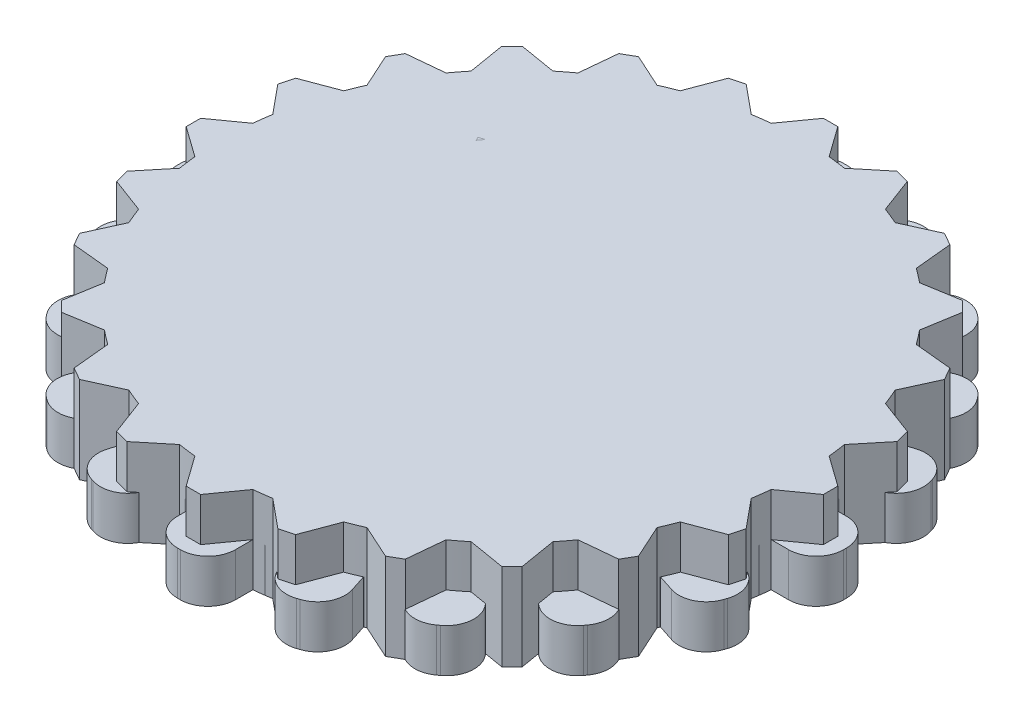
SolidWorks part; units mm, degrees
ref_plane "Front Plane" through (0, 0, 0) normal (0, 0, 1) x (1, 0, 0)
ref_plane "Top Plane" through (0, 0, 0) normal (0, 1, 0) x (1, 0, 0)
ref_plane "Right Plane" through (0, 0, 0) normal (1, 0, 0) x (0, 0, -1)
sketch "Sketch1" plane through (0, 0, 0) normal (0, 1, 0) x (1, 0, 0)
  line L86 (-3.1424, 4.8669) -> (1.8576, 4.8669)
  line L87 (-3.1424, 4.8669) -> (-3.1424, 1.8669)
  line L111 (-1.1424, 15.3669) -> (-0.1424, 15.3669)
  line L112 (-0.1424, 15.3669) -> (1.3576, 13.1649)
  line L113 (-1.1424, 15.3669) -> (-2.6424, 13.1649)
  line L114 (5.7906, 13.5092) -> (5.9886, 10.8522)
  line L115 (4.9246, 14.0092) -> (5.7906, 13.5092)
  line L116 (4.9246, 14.0092) -> (2.5245, 12.8522)
  line L117 (9.9999, 8.9339) -> (8.8429, 6.5338)
  line L118 (9.4999, 9.7999) -> (9.9999, 8.9339)
  line L119 (9.4999, 9.7999) -> (6.8429, 9.9979)
  line L120 (11.3576, 2.8669) -> (9.1556, 1.3669)
  line L121 (11.3576, 3.8669) -> (11.3576, 2.8669)
  line L122 (11.3576, 3.8669) -> (9.1556, 5.3669)
  line L123 (9.4999, -3.0661) -> (6.8429, -3.2641)
  line L124 (9.9999, -2.2001) -> (9.4999, -3.0661)
  line L125 (9.9999, -2.2001) -> (8.8429, 0.2)
  line L126 (4.9246, -7.2754) -> (2.5245, -6.1184)
  line L127 (5.7906, -6.7754) -> (4.9246, -7.2754)
  line L128 (5.7906, -6.7754) -> (5.9886, -4.1184)
  line L129 (-1.1424, -8.6331) -> (-2.6424, -6.4311)
  line L130 (-0.1424, -8.6331) -> (-1.1424, -8.6331)
  line L131 (-0.1424, -8.6331) -> (1.3576, -6.4311)
  line L132 (-7.0754, -6.7754) -> (-7.2734, -4.1184)
  line L133 (-6.2094, -7.2754) -> (-7.0754, -6.7754)
  line L134 (-6.2094, -7.2754) -> (-3.8093, -6.1184)
  line L135 (-11.2847, -2.2001) -> (-10.1277, 0.2)
  line L136 (-10.7847, -3.0661) -> (-11.2847, -2.2001)
  line L137 (-10.7847, -3.0661) -> (-8.1277, -3.2641)
  line L138 (-12.6424, 3.8669) -> (-10.4404, 5.3669)
  line L139 (-12.6424, 2.8669) -> (-12.6424, 3.8669)
  line L140 (-12.6424, 2.8669) -> (-10.4404, 1.3669)
  line L141 (-10.7847, 9.7999) -> (-8.1277, 9.9979)
  line L142 (-11.2847, 8.9339) -> (-10.7847, 9.7999)
  line L143 (-11.2847, 8.9339) -> (-10.1277, 6.5338)
  line L144 (-6.2094, 14.0092) -> (-3.8093, 12.8522)
  line L145 (-7.0754, 13.5092) -> (-6.2094, 14.0092)
  line L146 (-7.0754, 13.5092) -> (-7.2734, 10.8522)
  line L147 (-3.1424, 1.8669) -> (1.8576, 1.8669)
  line L148 (1.8576, 4.8669) -> (1.8576, 1.8669)
  line L149 (-3.1424, 4.8669) -> (1.8576, 1.8669) construction
  line L150 (-3.1424, 1.8669) -> (1.8576, 4.8669) construction
  arc A43 (-2.6424, 13.1649) -> (-3.8093, 12.8522) centre (-0.6424, 3.3669) ccw
  arc A44 (-7.2734, 10.8522) -> (-8.1277, 9.9979) centre (-0.6424, 3.3669) ccw
  arc A45 (-10.1277, 6.5338) -> (-10.4404, 5.3669) centre (-0.6424, 3.3669) ccw
  arc A46 (-10.4404, 1.3669) -> (-10.1277, 0.2) centre (-0.6424, 3.3669) ccw
  arc A47 (-8.1277, -3.2641) -> (-7.2734, -4.1184) centre (-0.6424, 3.3669) ccw
  arc A48 (-3.8093, -6.1184) -> (-2.6424, -6.4311) centre (-0.6424, 3.3669) ccw
  arc A49 (1.3576, -6.4311) -> (2.5245, -6.1184) centre (-0.6424, 3.3669) ccw
  arc A50 (5.9886, -4.1184) -> (6.8429, -3.2641) centre (-0.6424, 3.3669) ccw
  arc A51 (8.8429, 0.2) -> (9.1556, 1.3669) centre (-0.6424, 3.3669) ccw
  arc A52 (9.1556, 5.3669) -> (8.8429, 6.5338) centre (-0.6424, 3.3669) ccw
  arc A53 (6.8429, 9.9979) -> (5.9886, 10.8522) centre (-0.6424, 3.3669) ccw
  arc A54 (2.5245, 12.8522) -> (1.3576, 13.1649) centre (-0.6424, 3.3669) ccw
  point P6 (0, 0)
  point P8 (0, 0)
  point P9 (0, 0)
  point P12 (0, 2.7462)
  point P17 (0, 0)
  point P18 (0, 2.7462)
  point P22 (-2.5, 0.7462)
  point P63 (0, 0)
  point P68 (0, 0)
  point P69 (-0.6424, 3.3669)
  point P119 (0, 0)
  dimension "D1" = 20
  dimension "D2" = 3
  dimension "D3" = 5
  dimension "D8" = 12
sketch "Sketch2" plane through (0, 0, 0) normal (0, 1, 0) x (1, 0, 0)
  line L0 (-2, 0) -> (2, 0)
  line L1 (-23, -0.1) -> (-23, 0.1)
  line L2 (-21.1, 2) -> (-19.8997, 2)
  line L3 (-21.1, -2) -> (-19.8997, -2)
  line L4 (-20.6853, 4.6181) -> (-19.5438, 4.2472)
  line L5 (-19.4493, 8.4224) -> (-18.3078, 8.0515)
  line L6 (-21.9052, 7.0123) -> (-21.8434, 7.2025)
  line L7 (-18.2458, 10.7842) -> (-17.2748, 10.0787)
  line L8 (-15.8947, 14.0203) -> (-14.9237, 13.3148)
  line L9 (-18.6662, 13.4382) -> (-18.5486, 13.6)
  line L10 (-14.0203, 15.8947) -> (-13.3148, 14.9237)
  line L11 (-10.7842, 18.2458) -> (-10.0787, 17.2748)
  line L12 (-13.6, 18.5486) -> (-13.4382, 18.6662)
  line L13 (-8.4224, 19.4493) -> (-8.0515, 18.3078)
  line L14 (-4.6181, 20.6853) -> (-4.2472, 19.5438)
  line L15 (-7.2025, 21.8434) -> (-7.0123, 21.9052)
  line L16 (-2, 21.1) -> (-2, 19.8997)
  line L17 (2, 21.1) -> (2, 19.8997)
  line L18 (-0.1, 23) -> (0.1, 23)
  line L19 (4.6181, 20.6853) -> (4.2472, 19.5438)
  line L20 (8.4224, 19.4493) -> (8.0515, 18.3078)
  line L21 (7.0123, 21.9052) -> (7.2025, 21.8434)
  line L22 (10.7842, 18.2458) -> (10.0787, 17.2748)
  line L23 (14.0203, 15.8947) -> (13.3148, 14.9237)
  line L24 (13.4382, 18.6662) -> (13.6, 18.5486)
  line L25 (15.8947, 14.0203) -> (14.9237, 13.3148)
  line L26 (18.2458, 10.7842) -> (17.2748, 10.0787)
  line L27 (18.5486, 13.6) -> (18.6662, 13.4382)
  line L28 (19.4493, 8.4224) -> (18.3078, 8.0515)
  line L29 (20.6853, 4.6181) -> (19.5438, 4.2472)
  line L30 (21.8434, 7.2025) -> (21.9052, 7.0123)
  line L31 (21.1, 2) -> (19.8997, 2)
  line L32 (21.1, -2) -> (19.8997, -2)
  line L33 (23, 0.1) -> (23, -0.1)
  line L34 (20.6853, -4.6181) -> (19.5438, -4.2472)
  line L35 (19.4493, -8.4224) -> (18.3078, -8.0515)
  line L36 (21.9052, -7.0123) -> (21.8434, -7.2025)
  line L37 (18.2458, -10.7842) -> (17.2748, -10.0787)
  line L38 (15.8947, -14.0203) -> (14.9237, -13.3148)
  line L39 (18.6662, -13.4382) -> (18.5486, -13.6)
  line L40 (14.0203, -15.8947) -> (13.3148, -14.9237)
  line L41 (10.7842, -18.2458) -> (10.0787, -17.2748)
  line L42 (13.6, -18.5486) -> (13.4382, -18.6662)
  line L43 (8.4224, -19.4493) -> (8.0515, -18.3078)
  line L44 (4.6181, -20.6853) -> (4.2472, -19.5438)
  line L45 (7.2025, -21.8434) -> (7.0123, -21.9052)
  line L46 (2, -21.1) -> (2, -19.8997)
  line L47 (-2, -21.1) -> (-2, -19.8997)
  line L48 (0.1, -23) -> (-0.1, -23)
  line L49 (-4.6181, -20.6853) -> (-4.2472, -19.5438)
  line L50 (-8.4224, -19.4493) -> (-8.0515, -18.3078)
  line L51 (-7.0123, -21.9052) -> (-7.2025, -21.8434)
  line L52 (-10.7842, -18.2458) -> (-10.0787, -17.2748)
  line L53 (-14.0203, -15.8947) -> (-13.3148, -14.9237)
  line L54 (-13.4382, -18.6662) -> (-13.6, -18.5486)
  line L55 (-15.8947, -14.0203) -> (-14.9237, -13.3148)
  line L56 (-18.2458, -10.7842) -> (-17.2748, -10.0787)
  line L57 (-18.5486, -13.6) -> (-18.6662, -13.4382)
  line L58 (-19.4493, -8.4224) -> (-18.3078, -8.0515)
  line L59 (-20.6853, -4.6181) -> (-19.5438, -4.2472)
  line L60 (-21.8434, -7.2025) -> (-21.9052, -7.0123)
  arc A0 (-18.3078, -8.0515) -> (-17.2748, -10.0787) centre (0, 0) ccw
  arc A1 (-21.1, 2) -> (-23, 0.1) centre (-21.1, 0.1) ccw
  arc A2 (-21.1, -2) -> (-23, -0.1) centre (-21.1, -0.1) cw
  arc A3 (-20.6853, 4.6181) -> (-21.9052, 7.0123) centre (-20.0982, 6.4252) cw
  arc A4 (-19.4493, 8.4224) -> (-21.8434, 7.2025) centre (-20.0364, 6.6154) ccw
  arc A5 (-18.2458, 10.7842) -> (-18.6662, 13.4382) centre (-17.129, 12.3214) cw
  arc A6 (-15.8947, 14.0203) -> (-18.5486, 13.6) centre (-17.0115, 12.4832) ccw
  arc A7 (-14.0203, 15.8947) -> (-13.6, 18.5486) centre (-12.4832, 17.0115) cw
  arc A8 (-10.7842, 18.2458) -> (-13.4382, 18.6662) centre (-12.3214, 17.129) ccw
  arc A9 (-8.4224, 19.4493) -> (-7.2025, 21.8434) centre (-6.6154, 20.0364) cw
  arc A10 (-4.6181, 20.6853) -> (-7.0123, 21.9052) centre (-6.4252, 20.0982) ccw
  arc A11 (-2, 21.1) -> (-0.1, 23) centre (-0.1, 21.1) cw
  arc A12 (2, 21.1) -> (0.1, 23) centre (0.1, 21.1) ccw
  arc A13 (4.6181, 20.6853) -> (7.0123, 21.9052) centre (6.4252, 20.0982) cw
  arc A14 (8.4224, 19.4493) -> (7.2025, 21.8434) centre (6.6154, 20.0364) ccw
  arc A15 (10.7842, 18.2458) -> (13.4382, 18.6662) centre (12.3214, 17.129) cw
  arc A16 (14.0203, 15.8947) -> (13.6, 18.5486) centre (12.4832, 17.0115) ccw
  arc A17 (15.8947, 14.0203) -> (18.5486, 13.6) centre (17.0115, 12.4832) cw
  arc A18 (18.2458, 10.7842) -> (18.6662, 13.4382) centre (17.129, 12.3214) ccw
  arc A19 (19.4493, 8.4224) -> (21.8434, 7.2025) centre (20.0364, 6.6154) cw
  arc A20 (20.6853, 4.6181) -> (21.9052, 7.0123) centre (20.0982, 6.4252) ccw
  arc A21 (21.1, 2) -> (23, 0.1) centre (21.1, 0.1) cw
  arc A22 (21.1, -2) -> (23, -0.1) centre (21.1, -0.1) ccw
  arc A23 (20.6853, -4.6181) -> (21.9052, -7.0123) centre (20.0982, -6.4252) cw
  arc A24 (19.4493, -8.4224) -> (21.8434, -7.2025) centre (20.0364, -6.6154) ccw
  arc A25 (18.2458, -10.7842) -> (18.6662, -13.4382) centre (17.129, -12.3214) cw
  arc A26 (15.8947, -14.0203) -> (18.5486, -13.6) centre (17.0115, -12.4832) ccw
  arc A27 (14.0203, -15.8947) -> (13.6, -18.5486) centre (12.4832, -17.0115) cw
  arc A28 (10.7842, -18.2458) -> (13.4382, -18.6662) centre (12.3214, -17.129) ccw
  arc A29 (8.4224, -19.4493) -> (7.2025, -21.8434) centre (6.6154, -20.0364) cw
  arc A30 (4.6181, -20.6853) -> (7.0123, -21.9052) centre (6.4252, -20.0982) ccw
  arc A31 (2, -21.1) -> (0.1, -23) centre (0.1, -21.1) cw
  arc A32 (-2, -21.1) -> (-0.1, -23) centre (-0.1, -21.1) ccw
  arc A33 (-4.6181, -20.6853) -> (-7.0123, -21.9052) centre (-6.4252, -20.0982) cw
  arc A34 (-8.4224, -19.4493) -> (-7.2025, -21.8434) centre (-6.6154, -20.0364) ccw
  arc A35 (-10.7842, -18.2458) -> (-13.4382, -18.6662) centre (-12.3214, -17.129) cw
  arc A36 (-14.0203, -15.8947) -> (-13.6, -18.5486) centre (-12.4832, -17.0115) ccw
  arc A37 (-15.8947, -14.0203) -> (-18.5486, -13.6) centre (-17.0115, -12.4832) cw
  arc A38 (-18.2458, -10.7842) -> (-18.6662, -13.4382) centre (-17.129, -12.3214) ccw
  arc A39 (-19.4493, -8.4224) -> (-21.8434, -7.2025) centre (-20.0364, -6.6154) cw
  arc A40 (-20.6853, -4.6181) -> (-21.9052, -7.0123) centre (-20.0982, -6.4252) ccw
  arc A41 (-19.8997, -2) -> (-19.5438, -4.2472) centre (0, 0) ccw
  arc A42 (-19.5438, 4.2472) -> (-19.8997, 2) centre (0, 0) ccw
  arc A43 (-17.2748, 10.0787) -> (-18.3078, 8.0515) centre (0, 0) ccw
  arc A44 (-13.3148, 14.9237) -> (-14.9237, 13.3148) centre (0, 0) ccw
  arc A45 (-8.0515, 18.3078) -> (-10.0787, 17.2748) centre (0, 0) ccw
  arc A46 (-2, 19.8997) -> (-4.2472, 19.5438) centre (0, 0) ccw
  arc A47 (4.2472, 19.5438) -> (2, 19.8997) centre (0, 0) ccw
  arc A48 (10.0787, 17.2748) -> (8.0515, 18.3078) centre (0, 0) ccw
  arc A49 (14.9237, 13.3148) -> (13.3148, 14.9237) centre (0, 0) ccw
  arc A50 (18.3078, 8.0515) -> (17.2748, 10.0787) centre (0, 0) ccw
  arc A51 (19.8997, 2) -> (19.5438, 4.2472) centre (0, 0) ccw
  arc A52 (19.5438, -4.2472) -> (19.8997, -2) centre (0, 0) ccw
  arc A53 (17.2748, -10.0787) -> (18.3078, -8.0515) centre (0, 0) ccw
  arc A54 (13.3148, -14.9237) -> (14.9237, -13.3148) centre (0, 0) ccw
  arc A55 (8.0515, -18.3078) -> (10.0787, -17.2748) centre (0, 0) ccw
  arc A56 (2, -19.8997) -> (4.2472, -19.5438) centre (0, 0) ccw
  arc A57 (-10.0787, -17.2748) -> (-8.0515, -18.3078) centre (0, 0) ccw
  arc A58 (-4.2472, -19.5438) -> (-2, -19.8997) centre (0, 0) ccw
  arc A59 (-14.9237, -13.3148) -> (-13.3148, -14.9237) centre (0, 0) ccw
  point P6 (0, 0)
  point P10 (-23, 2)
  point P170 (0, 0)
  dimension "D1" = 40
  dimension "D4" = 1.9
  dimension "D5" = 20
extrude "Boss-Extrude3" add sketch "Sketch2" along normal blind 3 contours L55 A59 L53 A36 L54 A35 L52 A57 L50 A34 L51 A33 L49 A58 L47 A32 L48 A31 L46 A56 L44 A30 L45 A29 L43 A55 L41 A28 L42 A27 L40 A54 L38 A26 L39 A25 L37 A53 L35 A24 L36 A23 L34 A52 L32 A22 L33 A21 region at (-22.3495, 0, 0)
sketch "Sketch3" plane through (0, 0, 0) normal (0, 1, 0) x (1, 0, 0)
  line L0 (-22, 0) -> (22, 0)
  line L1 (22, -0.5) -> (22, 0.5)
  line L2 (22, 0.5) -> (19.8997, 2)
  line L3 (22, -0.5) -> (19.8997, -2)
  line L4 (21.3798, -5.2111) -> (19.7393, -3.2186)
  line L5 (21.121, -6.177) -> (21.3798, -5.2111)
  line L6 (21.121, -6.177) -> (18.704, -7.0823)
  line L7 (19.3026, -10.567) -> (18.2337, -8.2178)
  line L8 (18.8026, -11.433) -> (19.3026, -10.567)
  line L9 (18.8026, -11.433) -> (16.2337, -11.6819)
  line L10 (15.9099, -15.2028) -> (15.4855, -12.657)
  line L11 (15.2028, -15.9099) -> (15.9099, -15.2028)
  line L12 (15.2028, -15.9099) -> (12.657, -15.4855)
  line L13 (11.433, -18.8026) -> (11.6819, -16.2337)
  line L14 (10.567, -19.3026) -> (11.433, -18.8026)
  line L15 (10.567, -19.3026) -> (8.2178, -18.2337)
  line L16 (6.177, -21.121) -> (7.0823, -18.704)
  line L17 (5.2111, -21.3798) -> (6.177, -21.121)
  line L18 (5.2111, -21.3798) -> (3.2186, -19.7393)
  line L19 (0.5, -22) -> (2, -19.8997)
  line L20 (-0.5, -22) -> (0.5, -22)
  line L21 (-0.5, -22) -> (-2, -19.8997)
  line L22 (-5.2111, -21.3798) -> (-3.2186, -19.7393)
  line L23 (-6.177, -21.121) -> (-5.2111, -21.3798)
  line L24 (-6.177, -21.121) -> (-7.0823, -18.704)
  line L25 (-10.567, -19.3026) -> (-8.2178, -18.2337)
  line L26 (-11.433, -18.8026) -> (-10.567, -19.3026)
  line L27 (-11.433, -18.8026) -> (-11.6819, -16.2337)
  line L28 (-15.2028, -15.9099) -> (-12.657, -15.4855)
  line L29 (-15.9099, -15.2028) -> (-15.2028, -15.9099)
  line L30 (-15.9099, -15.2028) -> (-15.4855, -12.657)
  line L31 (-18.8026, -11.433) -> (-16.2337, -11.6819)
  line L32 (-19.3026, -10.567) -> (-18.8026, -11.433)
  line L33 (-19.3026, -10.567) -> (-18.2337, -8.2178)
  line L34 (-21.121, -6.177) -> (-18.704, -7.0823)
  line L35 (-21.3798, -5.2111) -> (-21.121, -6.177)
  line L36 (-21.3798, -5.2111) -> (-19.7393, -3.2186)
  line L37 (-22, -0.5) -> (-19.8997, -2)
  line L38 (-22, 0.5) -> (-22, -0.5)
  line L39 (-22, 0.5) -> (-19.8997, 2)
  line L40 (-21.3798, 5.2111) -> (-19.7393, 3.2186)
  line L41 (-21.121, 6.177) -> (-21.3798, 5.2111)
  line L42 (-21.121, 6.177) -> (-18.704, 7.0823)
  line L43 (-19.3026, 10.567) -> (-18.2337, 8.2178)
  line L44 (-18.8026, 11.433) -> (-19.3026, 10.567)
  line L45 (-18.8026, 11.433) -> (-16.2337, 11.6819)
  line L46 (-15.9099, 15.2028) -> (-15.4855, 12.657)
  line L47 (-15.2028, 15.9099) -> (-15.9099, 15.2028)
  line L48 (-15.2028, 15.9099) -> (-12.657, 15.4855)
  line L49 (-11.433, 18.8026) -> (-11.6819, 16.2337)
  line L50 (-10.567, 19.3026) -> (-11.433, 18.8026)
  line L51 (-10.567, 19.3026) -> (-8.2178, 18.2337)
  line L52 (-6.177, 21.121) -> (-7.0823, 18.704)
  line L53 (-5.2111, 21.3798) -> (-6.177, 21.121)
  line L54 (-5.2111, 21.3798) -> (-3.2186, 19.7393)
  line L55 (-0.5, 22) -> (-2, 19.8997)
  line L56 (0.5, 22) -> (-0.5, 22)
  line L57 (0.5, 22) -> (2, 19.8997)
  line L58 (5.2111, 21.3798) -> (3.2186, 19.7393)
  line L59 (6.177, 21.121) -> (5.2111, 21.3798)
  line L60 (6.177, 21.121) -> (7.0823, 18.704)
  line L61 (10.567, 19.3026) -> (8.2178, 18.2337)
  line L62 (11.433, 18.8026) -> (10.567, 19.3026)
  line L63 (11.433, 18.8026) -> (11.6819, 16.2337)
  line L64 (15.2028, 15.9099) -> (12.657, 15.4855)
  line L65 (15.9099, 15.2028) -> (15.2028, 15.9099)
  line L66 (15.9099, 15.2028) -> (15.4855, 12.657)
  line L67 (18.8026, 11.433) -> (16.2337, 11.6819)
  line L68 (19.3026, 10.567) -> (18.8026, 11.433)
  line L69 (19.3026, 10.567) -> (18.2337, 8.2178)
  line L70 (21.121, 6.177) -> (18.704, 7.0823)
  line L71 (21.3798, 5.2111) -> (21.121, 6.177)
  line L72 (21.3798, 5.2111) -> (19.7393, 3.2186)
  arc A0 (-8.2178, -18.2337) -> (-7.0823, -18.704) centre (0, 0) ccw
  arc A1 (-12.657, -15.4855) -> (-11.6819, -16.2337) centre (0, 0) ccw
  arc A2 (-16.2337, -11.6819) -> (-15.4855, -12.657) centre (0, 0) ccw
  arc A3 (-18.704, -7.0823) -> (-18.2337, -8.2178) centre (0, 0) ccw
  arc A4 (-19.8997, -2) -> (-19.7393, -3.2186) centre (0, 0) ccw
  arc A5 (-19.7393, 3.2186) -> (-19.8997, 2) centre (0, 0) ccw
  arc A6 (-18.2337, 8.2178) -> (-18.704, 7.0823) centre (0, 0) ccw
  arc A7 (-15.4855, 12.657) -> (-16.2337, 11.6819) centre (0, 0) ccw
  arc A8 (-11.6819, 16.2337) -> (-12.657, 15.4855) centre (0, 0) ccw
  arc A9 (-7.0823, 18.704) -> (-8.2178, 18.2337) centre (0, 0) ccw
  arc A10 (-2, 19.8997) -> (-3.2186, 19.7393) centre (0, 0) ccw
  arc A11 (3.2186, 19.7393) -> (2, 19.8997) centre (0, 0) ccw
  arc A12 (8.2178, 18.2337) -> (7.0823, 18.704) centre (0, 0) ccw
  arc A13 (12.657, 15.4855) -> (11.6819, 16.2337) centre (0, 0) ccw
  arc A14 (16.2337, 11.6819) -> (15.4855, 12.657) centre (0, 0) ccw
  arc A15 (18.704, 7.0823) -> (18.2337, 8.2178) centre (0, 0) ccw
  arc A16 (19.8997, 2) -> (19.7393, 3.2186) centre (0, 0) ccw
  arc A17 (19.7393, -3.2186) -> (19.8997, -2) centre (0, 0) ccw
  arc A18 (18.2337, -8.2178) -> (18.704, -7.0823) centre (0, 0) ccw
  arc A19 (-3.2186, -19.7393) -> (-2, -19.8997) centre (0, 0) ccw
  arc A20 (2, -19.8997) -> (3.2186, -19.7393) centre (0, 0) ccw
  arc A21 (7.0823, -18.704) -> (8.2178, -18.2337) centre (0, 0) ccw
  arc A22 (11.6819, -16.2337) -> (12.657, -15.4855) centre (0, 0) ccw
  arc A23 (15.4855, -12.657) -> (16.2337, -11.6819) centre (0, 0) ccw
  point P6 (0, 0)
  point P7 (0, -12.952)
  point P8 (-6.2727, 0)
  point P9 (11.4668, 0)
  point P10 (0, 0)
  point P108 (0, 0)
  dimension "D1" = 40
  dimension "D2" = 22
  dimension "D3" = 2
  dimension "D4" = 24
extrude "Boss-Extrude5" add sketch "Sketch3" along normal blind 6 separate body contours L2 A16 L72 L71 L70 A15 L69 L68 L67 A14 L66 L65 L64 A13 L63 L62 L61 A12 L60 L59 L58 A11 L57 L56 L55 A10 L54 L53 L52 A9 L51 L50 L49 A8 L48 L47 L46 A7 L45 L44 L43 A6 L42 L41 L40 A5 L39 L38 L0 L1 | L10 A23 L9 L8 L7 A18 L6 L5 L4 A17 L3 L1 L0 L38 L37 A4 L36 L35 L34 A3 L33 L32 L31 A2 L30 L29 L28 A1 L27 L26 L25 A0 L24 L23 L22 A19 L21 L20 L19 A20 L18 L17 L16 A21 L15 L14 L13 A22 L12 L11 region at (0, 0, -8.8989) region at (0, 0, 8.8989)
extrude "Boss-Extrude6" add sketch "Sketch1" along normal blind 6 separate body
sketch "Sketch5" plane through (0, 6, 0) normal (0, 1, 0) x (1, 0, 0)
  line L0 (-0.6424, 15.3669) -> (-0.6424, -8.6331) construction
  line L1 (-0.1424, 15.3669) -> (-1.1424, 15.3669) construction
  line L2 (-1.1424, -8.6331) -> (-0.1424, -8.6331) construction
  line L3 (11.3576, 3.3669) -> (-12.6424, 3.3669) construction
  line L4 (11.3576, 2.8669) -> (11.3576, 3.8669) construction
  line L5 (-12.6424, 3.8669) -> (-12.6424, 2.8669) construction
  circle A0 centre (-0.6424, 3.3669) radius 5.1751
